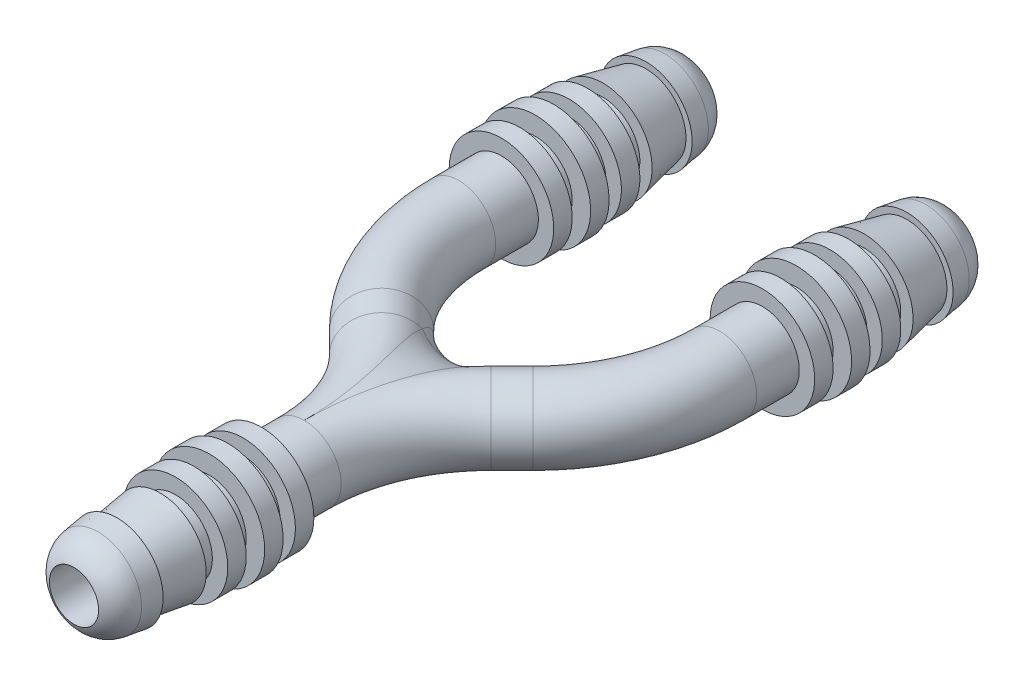
SolidWorks part; units mm, degrees
ref_plane "Front Plane" through (0, 0, 0) normal (0, 0, 1) x (1, 0, 0)
ref_plane "Top Plane" through (0, 0, 0) normal (0, 1, 0) x (1, 0, 0)
ref_plane "Right Plane" through (0, 0, 0) normal (1, 0, 0) x (0, 0, -1)
sketch "Sketch1" plane through (0, 0, 0) normal (0, 1, 0) x (1, 0, 0)
  line L0 (0, -12.5637) -> (0, -50)
  line L1 (8.8839, 8.8839) -> (12.3293, 12.3293)
  line L2 (21.2132, 33.7769) -> (21.2132, 71.2132)
  arc A0 (21.2132, 33.7769) -> (12.3293, 12.3293) centre (-9.1182, 33.7769) cw
  arc A1 (8.8839, 8.8839) -> (0, -12.5637) centre (30.3314, -12.5637) ccw
  point P7 (21.2132, 21.2132)
  point P10 (0, 0)
  dimension "D6" = 30.3314
  dimension "D1" = 50
  dimension "D2" = 30
  dimension "D3" = 135
  dimension "D4" = 50
  dimension "D5" = 135
sketch "Sketch10" plane through (0, 0, 0) normal (0, 1, 0) x (1, 0, 0)
  line L0 (0, -50) -> (0, -12.5637)
  line L1 (-8.8839, 8.8839) -> (-12.3293, 12.3293)
  line L2 (-21.2132, 33.7769) -> (-21.2132, 71.2132)
  arc A0 (0, -12.5637) -> (-8.8839, 8.8839) centre (-30.3314, -12.5637) ccw
  arc A1 (-12.3293, 12.3293) -> (-21.2132, 33.7769) centre (9.1182, 33.7769) cw
  point P8 (0, 0)
  point P11 (-21.2132, 21.2132)
  dimension "D6" = 30.3314
  dimension "D1" = 50
  dimension "D2" = 50
  dimension "D3" = 30
  dimension "D4" = 135
  dimension "D5" = 135
ref_plane "Plane5" through (0, 0, 50) normal (0, 0, 1) x (1, 0, 0)
sketch "Sketch11" plane through (0, 0, 50) normal (0, 0, 1) x (1, 0, 0)
  circle A0 centre (0, 0) radius 6
sweep "Sweep2" add profiles "Sketch11" path "Sketch1"
sketch "Sketch12" plane through (0, 0, 50) normal (0, 0, 1) x (1, 0, 0)
  circle A0 centre (0, 0) radius 6
sweep "Sweep3" add profiles "Sketch12" path "Sketch10"
sketch "Sketch14" plane through (0, 0, 0) normal (0, 1, 0) x (1, 0, 0)
  line L0 (0, -50) -> (0, -12.4264)
  line L1 (-8.173, -50) -> (8.173, -50) construction
  line L2 (8.7868, 8.7868) -> (12.4264, 12.4264)
  line L3 (21.2132, 33.6396) -> (21.2132, 71.2132)
  line L4 (27.2132, 71.2132) -> (15.2132, 71.2132) construction
  arc A0 (21.2132, 33.6396) -> (12.4264, 12.4264) centre (-8.7868, 33.6396) cw
  arc A1 (8.7868, 8.7868) -> (0, -12.4264) centre (30, -12.4264) ccw
  point P11 (21.2132, 21.2132)
  point P14 (0, 0)
  dimension "D6" = 30
  dimension "D1" = 50
  dimension "D2" = 50
  dimension "D3" = 135
  dimension "D4" = 135
  dimension "D5" = 30
sketch "Sketch15" plane through (0, 0, 0) normal (0, 1, 0) x (1, 0, 0)
  line L0 (-21.2132, 71.2132) -> (-21.2132, 33.6396)
  line L1 (-15.2132, 71.2132) -> (-27.2132, 71.2132) construction
  line L2 (-12.4264, 12.4264) -> (-8.7868, 8.7868)
  line L3 (0, -12.4264) -> (0, -50)
  arc A0 (0, -12.4264) -> (-8.7868, 8.7868) centre (-30, -12.4264) ccw
  arc A1 (-12.4264, 12.4264) -> (-21.2132, 33.6396) centre (8.7868, 33.6396) cw
  point P10 (0, 0)
  point P13 (-21.2132, 21.2132)
  dimension "D6" = 30
  dimension "D1" = 50
  dimension "D2" = 30
  dimension "D3" = 50
  dimension "D4" = 135
  dimension "D5" = 135
sketch "Sketch16" plane through (0, 0, 50) normal (0, 0, 1) x (1, 0, 0)
  circle A0 centre (0, 0) radius 4
sweep "Cut-Sweep1" cut profiles "Sketch16" path "Sketch14"
sketch "Sketch17" plane through (0, 0, 50) normal (0, 0, 1) x (1, 0, 0)
  circle A0 centre (0, 0) radius 4
sweep "Cut-Sweep2" cut profiles "Sketch17" path "Sketch15"
sketch "Sketch18" plane through (0, 0, 0) normal (0, 1, 0) x (1, 0, 0)
  line L0 (27.2132, 71.2132) -> (27.2132, 64.2132)
  line L1 (27.2132, 71.2132) -> (15.2132, 71.2132) construction
  line L2 (27.2132, 33.7769) -> (27.2132, 71.2132) construction
  line L3 (27.2132, 64.2132) -> (28.7132, 64.2132)
  line L4 (28.7132, 64.2132) -> (27.7132, 71.2132)
  line L5 (27.7132, 71.2132) -> (27.2132, 71.2132)
  dimension "D1" = 7
  dimension "D2" = 1.5
  dimension "D3" = 0.5
ref_plane "Plane6" through (0, 0, -71.2132) normal (0, 0, -1) x (-1, 0, 0)
sketch "Sketch22" plane through (0, 0, -71.2132) normal (0, 0, -1) x (-1, 0, 0)
  circle A0 centre (-21.2132, 0) radius 4
ref_axis "Axis1" through (21.2132, 0, -71.2132) along (0, 0, 1)
sketch "Sketch23" plane through (0, 0, -71.2132) normal (0, 0, -1) x (-1, 0, 0)
  circle A0 centre (21.2132, 0) radius 4
ref_axis "Axis2" through (-21.2132, 0, -71.2132) along (0, 0, 1)
revolve "Revolve1" add sketch "Sketch18" angle 360 about axis through (21.2132, 0, -71.2132) along (0, 0, 1)
sketch "Sketch24" plane through (0, 0, 0) normal (0, 1, 0) x (1, 0, 0)
  line L0 (-15.2132, 71.2132) -> (-15.2132, 64.2132)
  line L1 (-15.2132, 33.7769) -> (-15.2132, 71.2132) construction
  line L2 (-15.2132, 64.2132) -> (-13.7132, 64.2132)
  line L3 (-13.7132, 64.2132) -> (-14.7132, 71.2132)
  line L4 (-14.7132, 71.2132) -> (-15.2132, 71.2132)
  dimension "D1" = 1.5
  dimension "D2" = 0.5
  dimension "D3" = 7
revolve "Revolve2" add sketch "Sketch24" angle 360 about axis through (-21.2132, 0, -71.2132) along (0, 0, 1)
sketch "Sketch25" plane through (0, 0, 0) normal (0, 1, 0) x (1, 0, 0)
  line L0 (27.2132, 64.2132) -> (27.2132, 57.2132)
  line L1 (27.2132, 33.7769) -> (27.2132, 64.2132) construction
  line L2 (27.2132, 57.2132) -> (29.2132, 57.2132)
  line L3 (29.2132, 57.2132) -> (27.7132, 64.2132)
  line L4 (13.7132, 64.2132) -> (28.7132, 64.2132) construction
  line L5 (27.7132, 64.2132) -> (27.2132, 64.2132)
  dimension "D1" = 7
  dimension "D2" = 2
  dimension "D3" = 0.5
revolve "Revolve3" add sketch "Sketch25" angle 360 about axis through (21.2132, 0, -71.2132) along (0, 0, 1)
sketch "Sketch26" plane through (0, 0, 0) normal (0, 1, 0) x (1, 0, 0)
  line L0 (-15.2132, 64.2132) -> (-15.2132, 57.2132)
  line L1 (-15.2132, 33.7769) -> (-15.2132, 64.2132) construction
  line L2 (-15.2132, 57.2132) -> (-13.2132, 57.2132)
  line L3 (-13.2132, 57.2132) -> (-14.7132, 64.2132)
  line L4 (-28.7132, 64.2132) -> (-13.7132, 64.2132) construction
  line L5 (-14.7132, 64.2132) -> (-15.2132, 64.2132)
  dimension "D1" = 7
  dimension "D2" = 2
  dimension "D3" = 0.5
revolve "Revolve4" add sketch "Sketch26" angle 360 about axis through (-21.2132, 0, -71.2132) along (0, 0, 1)
sketch "Sketch27" plane through (0, 0, 0) normal (0, 1, 0) x (1, 0, 0)
  line L0 (6, -50) -> (6, -43)
  line L1 (-9.9, -50) -> (9.9, -50) construction
  line L2 (6, -50) -> (6, -12.5637) construction
  line L3 (6, -43) -> (7.5, -43)
  line L4 (7.5, -43) -> (6.5, -50)
  line L5 (6.5, -50) -> (6, -50)
  dimension "D1" = 7
  dimension "D2" = 1.5
  dimension "D3" = 0.5
sketch "Sketch29" plane through (0, 0, 0) normal (0, 1, 0) x (1, 0, 0)
  line L0 (27.2132, 57.2132) -> (27.2132, 54.7132)
  line L1 (27.2132, 33.7769) -> (27.2132, 57.2132) construction
  line L2 (27.2132, 54.7132) -> (29.7132, 54.7132)
  line L3 (29.7132, 54.7132) -> (29.7132, 51.7132)
  line L4 (29.7132, 51.7132) -> (27.2132, 51.7132)
  line L5 (27.2132, 51.7132) -> (27.2132, 54.7132)
  point P5 (28.4632, 51.7132)
  dimension "D1" = 2.5
  dimension "D2" = 3
  dimension "D3" = 2.5
revolve "Revolve7" add sketch "Sketch29" angle 360 about axis through (21.2132, 0, -71.2132) along (0, 0, 1) region at (28.4632, 0, -53.2132)
sketch "Sketch30" plane through (0, 0, 0) normal (0, 1, 0) x (1, 0, 0)
  line L0 (27.2132, 51.7132) -> (27.2132, 49.2132)
  line L1 (27.2132, 33.7769) -> (27.2132, 51.7132) construction
  line L2 (27.2132, 49.2132) -> (30.2132, 49.2132)
  line L3 (30.2132, 49.2132) -> (30.2132, 46.2132)
  line L4 (30.2132, 46.2132) -> (27.2132, 46.2132)
  line L5 (27.2132, 46.2132) -> (27.2132, 49.2132)
  dimension "D1" = 3
  dimension "D2" = 2.5
  dimension "D3" = 3
revolve "Revolve8" add sketch "Sketch30" angle 360 about axis through (21.2132, 0, -71.2132) along (0, 0, 1) region at (28.7132, 0, -47.7132)
sketch "Sketch31" plane through (0, 0, 0) normal (0, 1, 0) x (1, 0, 0)
  line L0 (27.2132, 46.2132) -> (27.2132, 43.7132)
  line L1 (27.2132, 33.7769) -> (27.2132, 46.2132) construction
  line L2 (27.2132, 43.7132) -> (29.7132, 43.7132)
  line L3 (29.7132, 43.7132) -> (29.7132, 40.7132)
  line L4 (29.7132, 40.7132) -> (27.2132, 40.7132)
  line L5 (27.2132, 40.7132) -> (27.2132, 43.7132)
  dimension "D1" = 3
  dimension "D2" = 2.5
  dimension "D3" = 2.5
revolve "Revolve9" add sketch "Sketch31" angle 360 about axis through (21.2132, 0, -71.2132) along (0, 0, 1) region at (28.4632, 0, -42.2132)
ref_plane "Plane10" through (-21.2132, 0, 0) normal (1, 0, 0) x (0, 0, -1)
ref_plane "Plane11" through (0, 0, -54.7132) normal (0, 0, -1) x (-1, 0, 0)
sketch "Sketch37" plane through (0, 0, -54.7132) normal (0, 0, -1) x (-1, 0, 0)
  circle A0 centre (21.2132, 0) radius 6
  circle A1 centre (21.2132, 0) radius 8.5
extrude "Boss-Extrude1" add sketch "Sketch37" against normal blind 3
ref_plane "Plane12" through (0, 0, -49.2132) normal (0, 0, -1) x (-1, 0, 0)
sketch "Sketch38" plane through (0, 0, -49.2132) normal (0, 0, -1) x (-1, 0, 0)
  circle A0 centre (21.2132, 0) radius 6
  circle A1 centre (21.2132, 0) radius 9
extrude "Boss-Extrude2" add sketch "Sketch38" against normal blind 3
ref_plane "Plane13" through (0, 0, -43.7132) normal (0, 0, -1) x (-1, 0, 0)
sketch "Sketch39" plane through (0, 0, -43.7132) normal (0, 0, -1) x (-1, 0, 0)
  circle A0 centre (21.2132, 0) radius 6
  circle A1 centre (21.2132, 0) radius 8.5
extrude "Boss-Extrude3" add sketch "Sketch39" against normal blind 3
ref_plane "Plane14" through (0, 0, 33.5) normal (0, 0, 1) x (1, 0, 0)
sketch "Sketch40" plane through (0, 0, 33.5) normal (0, 0, 1) x (1, 0, 0)
  circle A0 centre (0, 0) radius 6
  circle A1 centre (0, 0) radius 8.5
extrude "Boss-Extrude4" add sketch "Sketch40" against normal blind 3
ref_plane "Plane15" through (0, 0, 28) normal (0, 0, 1) x (1, 0, 0)
sketch "Sketch42" plane through (0, 0, 28) normal (0, 0, 1) x (1, 0, 0)
  circle A0 centre (0, 0) radius 6
  circle A1 centre (0, 0) radius 9
extrude "Boss-Extrude5" add sketch "Sketch42" against normal blind 3
ref_plane "Plane16" through (0, 0, 22.5) normal (0, 0, 1) x (1, 0, 0)
sketch "Sketch43" plane through (0, 0, 22.5) normal (0, 0, 1) x (1, 0, 0)
  circle A0 centre (0, 0) radius 6
  circle A1 centre (0, 0) radius 8.5
extrude "Boss-Extrude6" add sketch "Sketch43" against normal blind 3
ref_axis "Axis4" through (0, 0, -77.2739) along (0, 0, 1)
revolve "Revolve10" add sketch "Sketch27" angle 360 about axis through (0, 0, -77.2739) along (0, 0, 1)
sketch "Sketch45" plane through (0, 0, 0) normal (0, 1, 0) x (1, 0, 0)
  line L0 (6, -43) -> (6.5, -43)
  line L1 (7.5, -43) -> (-7.5, -43) construction
  line L2 (6.5, -43) -> (7.5, -36)
  line L3 (7.5, -36) -> (6, -36)
  line L4 (6, -43) -> (6, -33.5) construction
  line L5 (6, -36) -> (6, -43)
  dimension "D1" = 7
  dimension "D2" = 0.5
  dimension "D3" = 1.5
revolve "Revolve11" add sketch "Sketch45" angle 360 about axis through (0, 0, -77.2739) along (0, 0, 1)
fillet "Fillet2" radius 5 3 edges at (-27.7132, 0, -71.2132) (14.7132, 0, -71.2132) (-6.5, 0, 50)
fillet "Fillet3" radius 10 1 edges at (0, -0.5751, -7.3855)
